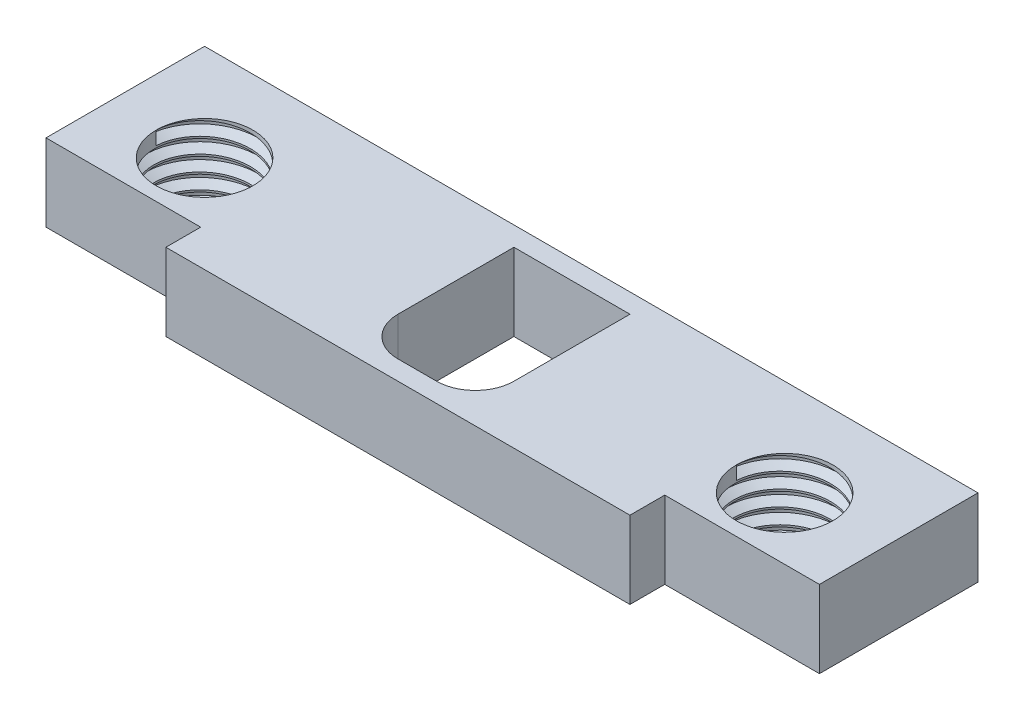
SolidWorks part; units mm, degrees
ref_plane "Front Plane" through (0, 0, 0) normal (0, 0, 1) x (1, 0, 0)
ref_plane "Top Plane" through (0, 0, 0) normal (0, 1, 0) x (1, 0, 0)
ref_plane "Right Plane" through (0, 0, 0) normal (1, 0, 0) x (0, 0, -1)
sketch "Sketch1" plane through (0, 0, 0) normal (0, 1, 0) x (1, 0, 0)
  line L0 (0, 102.1681) -> (0, -128.7692) construction
  line L1 (-100, 25) -> (100, 25)
  line L2 (-100, 25) -> (-100, -25)
  line L3 (-100, -25) -> (100, -25)
  line L4 (100, 25) -> (100, -25)
  line L5 (-100, 25) -> (100, -25) construction
  line L6 (-100, -25) -> (100, 25) construction
  line L7 (-15, 20) -> (15, 20)
  line L8 (-15, 20) -> (-15, -10)
  line L9 (-5, -20) -> (5, -20)
  line L10 (15, 20) -> (15, -10)
  line L11 (-15, 20) -> (15, -20) construction
  line L12 (-15, -20) -> (15, 20) construction
  arc A0 (5, -20) -> (15, -10) centre (5, -10) ccw
  arc A1 (-15, -10) -> (-5, -20) centre (-5, -10) ccw
  circle A2 centre (-75, 0) radius 12.5
  circle A3 centre (75, 0) radius 12.5
  point P0 (0, 0)
  point P7 (0, 0)
  dimension "D5" = 10
  dimension "D6" = 25
  dimension "D1" = 50
  dimension "D2" = 200
  dimension "D3" = 40
  dimension "D4" = 30
  dimension "D7" = 75
extrude "Boss-Extrude1" add sketch "Sketch1" along normal blind 20
thread "Thread1" pitch 4 method cut profile "Thread Profile1" start angle 0, offset 0, length 0, pitch 4, diameter 25
ref_plane "Plane1" through (-87.5, 20, 0) normal (0, 0, -1) x (1, 0, 0)
sketch "Thread Profile1" plane through (-87.5, 20, 0) normal (0, 0, -1) x (1, 0, 0)
  line L0 (0, 0) -> (0, 4) construction
  line L11 (0, 0) -> (0, 3.5)
  line L12 (0, 3.5) -> (-2.1651, 2.25)
  line L13 (-2.1651, 2.25) -> (-2.1651, 1.25)
  line L15 (-2.1651, 1.25) -> (0, 0)
  line L17 (-2.1651, 1.75) -> (0, 1.75) construction
  point P2 (0, 0)
  dimension "Pitch" = 4
  dimension "Profile_Angle" = 60
  dimension "Profile_Land" = 1
  dimension "Profile_Height" = 2.1651
thread "Thread2" pitch 4 method cut profile "Thread Profile2" start angle 0, offset 0, length 0, pitch 4, diameter 25
ref_plane "Plane2" through (62.5, 20, 0) normal (0, 0, -1) x (1, 0, 0)
sketch "Thread Profile2" plane through (62.5, 20, 0) normal (0, 0, -1) x (1, 0, 0)
  line L0 (0, 0) -> (0, 4) construction
  line L11 (0, 0) -> (0, 3.5)
  line L12 (0, 3.5) -> (-2.1651, 2.25)
  line L13 (-2.1651, 2.25) -> (-2.1651, 1.25)
  line L15 (-2.1651, 1.25) -> (0, 0)
  line L17 (-2.1651, 1.75) -> (0, 1.75) construction
  point P2 (0, 0)
  dimension "Pitch" = 4
  dimension "Profile_Angle" = 60
  dimension "Profile_Land" = 1
  dimension "Profile_Height" = 2.1651
sketch "Sketch2" plane through (0, 20, 0) normal (0, 1, 0) x (1, 0, 0)
  line L0 (-100, 25) -> (-100, -25) construction
  line L1 (-100, -16) -> (-60, -16)
  line L2 (-100, -16) -> (-100, -25)
  line L3 (-100, -25) -> (-60, -25)
  line L4 (-60, -16) -> (-60, -25)
  line L5 (-100, -25) -> (100, -25) construction
  line L6 (0, 43.7794) -> (0, -54.4313) construction
  line L7 (100, -25) -> (60, -25)
  line L8 (60, -16) -> (60, -25)
  line L9 (100, -16) -> (60, -16)
  line L10 (100, -16) -> (100, -25)
  dimension "D1" = 40
  dimension "D2" = 9
extrude "Cut-Extrude1" cut sketch "Sketch2" against normal through all
